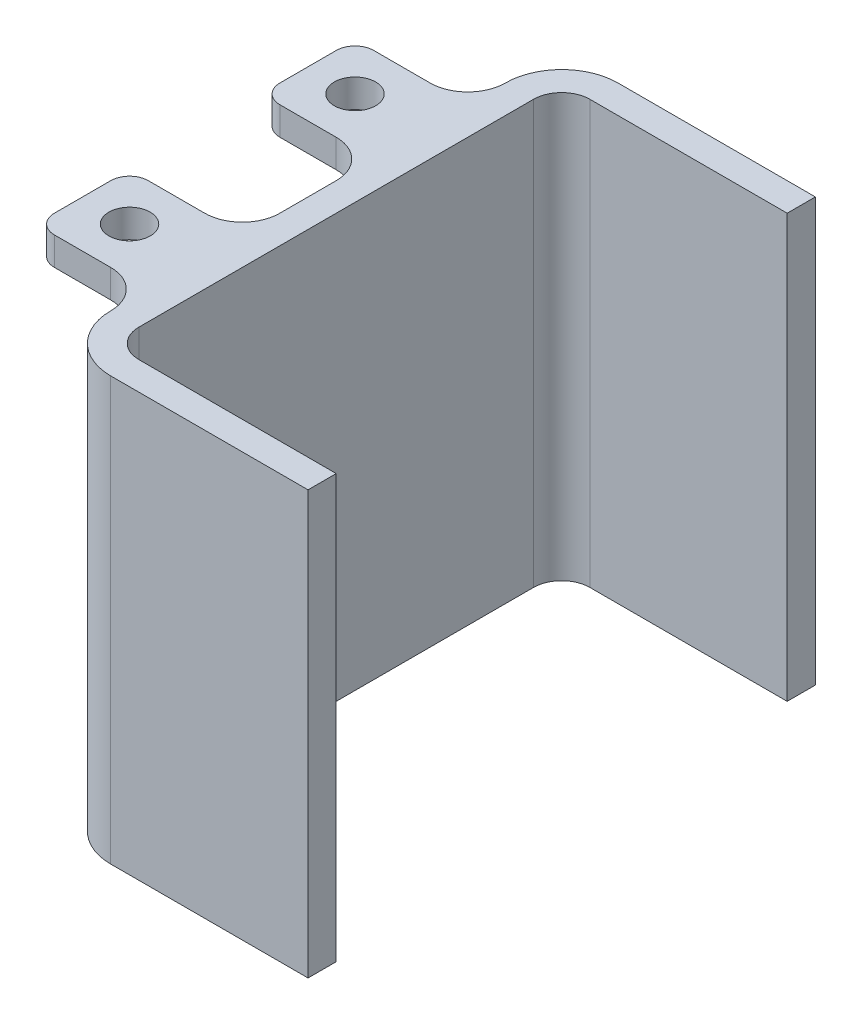
SolidWorks part; units mm, degrees
ref_plane "Front Plane" through (0, 0, 0) normal (0, 0, 1) x (1, 0, 0)
ref_plane "Top Plane" through (0, 0, 0) normal (0, 1, 0) x (1, 0, 0)
ref_plane "Right Plane" through (0, 0, 0) normal (1, 0, 0) x (0, 0, -1)
sketch "Sketch2" plane through (0, 0, 0) normal (0, 1, 0) x (1, 0, 0)
  line L0 (-6, 30) -> (6, 30)
  line L1 (6, 30) -> (6, 24)
  line L2 (6, 24) -> (2, 24)
  line L3 (2, 24) -> (2, -24)
  line L4 (2, -24) -> (6, -24)
  line L5 (6, -24) -> (6, -30)
  line L6 (6, -30) -> (-6, -30)
  line L7 (-6, -30) -> (-6, -24)
  line L8 (-6, -24) -> (-2, -24)
  line L9 (-2, -24) -> (-2, 24)
  line L10 (-2, 24) -> (-6, 24)
  line L11 (-6, 24) -> (-6, 30)
  dimension "D2" = 60
  dimension "D3" = 6
  dimension "D4" = 4
sketch "Sketch3" plane through (0, 0, 0) normal (0, 1, 0) x (1, 0, 0)
  line L5 (-8, 24) -> (-8, -24) construction
  line L6 (-8, 24) -> (-29, 24)
  line L7 (-32, 21) -> (-32, -21)
  line L8 (-29, -24) -> (-8, -24)
  line L16 (-8, 27) -> (-29, 27)
  line L17 (-35, 21) -> (-35, -21)
  line L18 (-29, -27) -> (-8, -27)
  line L19 (-8, 27) -> (-8, 24)
  line L20 (-8, -24) -> (-8, -27)
  arc A10 (-29, -24) -> (-32, -21) centre (-29, -21) cw
  arc A11 (-32, 21) -> (-29, 24) centre (-29, 21) cw
  arc A12 (-35, 21) -> (-29, 27) centre (-29, 21) cw
  arc A13 (-29, -27) -> (-35, -21) centre (-29, -21) cw
  point P2 (-8, 0)
  point P9 (-32, 24)
  dimension "D4" = 3
  dimension "D1" = 2
  dimension "D2" = 48
  dimension "D3" = 24
  dimension "D5" = 3
extrude "Boss-Extrude1" add sketch "Sketch3" along normal blind 45
sketch "Sketch4" plane through (0, 45, 0) normal (0, 1, 0) x (1, 0, 0)
  line L0 (-35, 21) -> (-35, -21) construction
  line L1 (-47, 17) -> (-35, 17)
  line L2 (-47, 17) -> (-47, 7)
  line L3 (-47, 7) -> (-35, 7)
  line L4 (-35, 17) -> (-35, 7)
  line L6 (-35, -7) -> (-47, -7)
  line L7 (-35, -7) -> (-35, -17)
  line L8 (-35, -17) -> (-47, -17)
  line L9 (-47, -7) -> (-47, -17)
  circle A0 centre (-42, 12) radius 2.2
  circle A1 centre (-42, -12) radius 2.2
  point P8 (-47, 12)
  point P16 (-47, -12)
  dimension "D2" = 4.4
  dimension "D6" = 4.4
  dimension "D1" = 5
  dimension "D3" = 12
  dimension "D4" = 10
  dimension "D5" = 10
  dimension "D7" = 12
  dimension "D8" = 12
extrude "Boss-Extrude2" add sketch "Sketch4" against normal blind 3
fillet "Fillet1" radius 4 4 edges at (-35, 43.5, 17) (-35, 43.5, 7) (-35, 43.5, -17) (-35, 43.5, -7)
fillet "Fillet2" radius 2 2 edges at (-35, 42, 12) (-35, 42, -12)
fillet "Fillet3" radius 2 4 edges at (-47, 43.5, 17) (-47, 43.5, 7) (-47, 43.5, -7) (-47, 43.5, -17)
